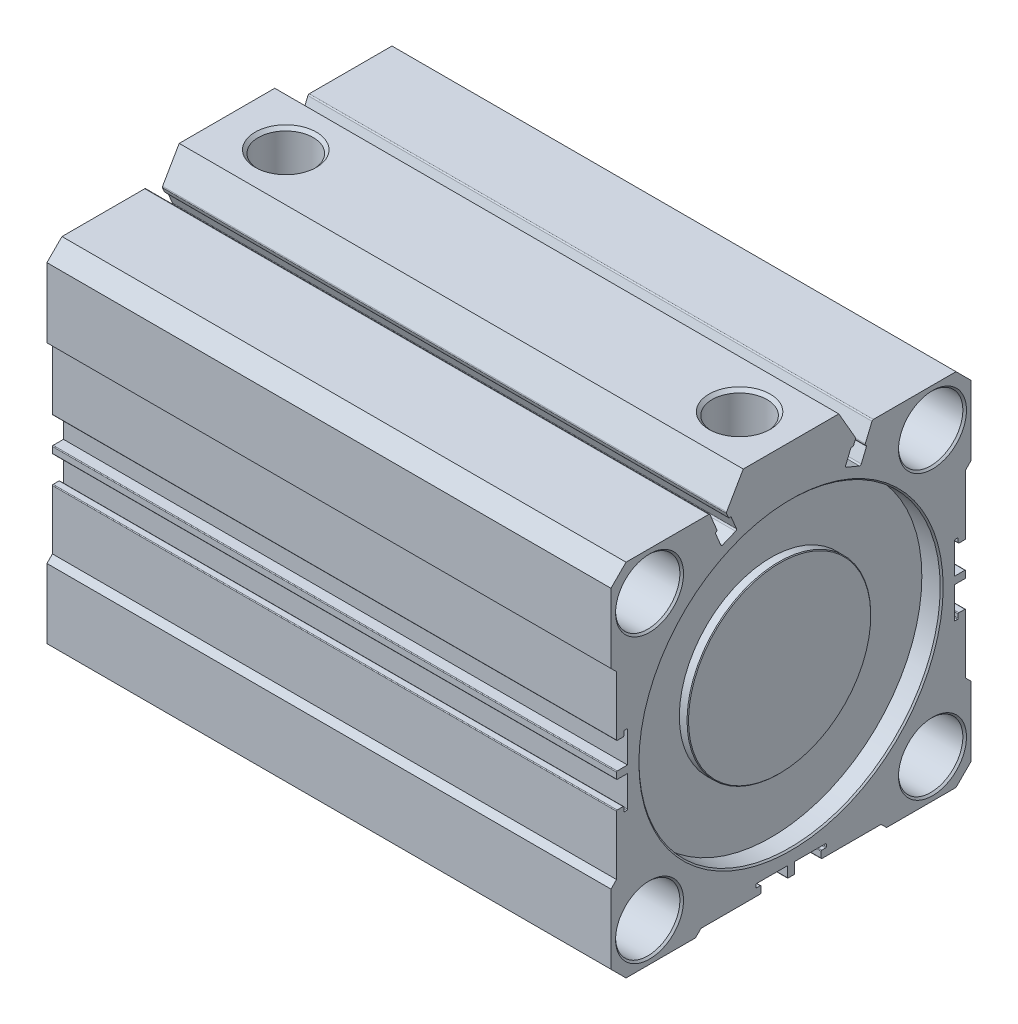
SolidWorks part; units mm, degrees
ref_plane "前视基准面" through (0, 0, 0) normal (0, 0, 1) x (1, 0, 0)
ref_plane "上视基准面" through (0, 0, 0) normal (0, 1, 0) x (1, 0, 0)
ref_plane "右视基准面" through (0, 0, 0) normal (1, 0, 0) x (0, 0, -1)
sketch "草图1" plane through (0, 0, 0) normal (1, 0, 0) x (0, 0, -1)
  line L0 (-49, -44.9) -> (-44.9, -49)
  line L1 (-44.9, -49) -> (-26, -49)
  line L2 (-26, -49) -> (-24.5, -47.5)
  line L3 (-24.5, -47.5) -> (-8.4, -47.5)
  line L4 (-8.2, -47.3) -> (-8.2, -45.7)
  line L5 (-8.4, -45.5) -> (-9.4, -45.5)
  line L6 (-9.6, -45.3) -> (-9.6, -44.7)
  line L7 (-9.4, -44.5) -> (-1, -44.5)
  line L8 (-1, -44.5) -> (-1, -47.3)
  line L9 (-0.8, -47.5) -> (0.8, -47.5)
  line L10 (1, -47.3) -> (1, -44.5)
  line L11 (1, -44.5) -> (9.4, -44.5)
  line L12 (9.6, -44.7) -> (9.6, -45.3)
  line L13 (9.4, -45.5) -> (8.4, -45.5)
  line L14 (8.2, -45.7) -> (8.2, -47.3)
  line L15 (8.4, -47.5) -> (24.5, -47.5)
  line L16 (24.5, -47.5) -> (26, -49)
  line L17 (26, -49) -> (44.9, -49)
  line L18 (44.9, -49) -> (49, -44.9)
  line L19 (49, -44.9) -> (49, -26)
  line L20 (49, -26) -> (47.5, -24.5)
  line L21 (47.5, -24.5) -> (47.5, -8.4)
  line L22 (47.3, -8.2) -> (45.7, -8.2)
  line L23 (45.5, -8.4) -> (45.5, -9.4)
  line L24 (45.3, -9.6) -> (44.7, -9.6)
  line L25 (44.5, -9.4) -> (44.5, -1)
  line L26 (44.5, -1) -> (47.3, -1)
  line L27 (47.5, -0.8) -> (47.5, 0.8)
  line L28 (47.3, 1) -> (44.5, 1)
  line L29 (44.5, 1) -> (44.5, 9.4)
  line L30 (44.7, 9.6) -> (45.3, 9.6)
  line L31 (45.5, 9.4) -> (45.5, 8.4)
  line L32 (45.7, 8.2) -> (47.3, 8.2)
  line L33 (47.5, 8.4) -> (47.5, 24.5)
  line L34 (47.5, 24.5) -> (49, 26)
  line L35 (49, 26) -> (49, 44.9)
  line L36 (49, 44.9) -> (44.9, 49)
  line L37 (44.9, 49) -> (22.4038, 49)
  line L38 (22.0343, 48.7531) -> (20.2073, 44.3424)
  line L39 (20.532, 43.5584) -> (19.1161, 40.1401)
  line L40 (18.5934, 39.9236) -> (15.0827, 41.3778)
  line L41 (14.8662, 41.9004) -> (16.2822, 45.3188)
  line L42 (17.0661, 45.6435) -> (17.5487, 46.8085)
  line L43 (17.5255, 47.1616) -> (13, 55)
  line L44 (13, 55) -> (-13, 55)
  line L45 (-13, 55) -> (-17.5255, 47.1616)
  line L46 (-17.5487, 46.8085) -> (-17.0661, 45.6435)
  line L47 (-16.2822, 45.3188) -> (-14.8662, 41.9004)
  line L48 (-15.0827, 41.3778) -> (-18.5934, 39.9236)
  line L49 (-19.1161, 40.1401) -> (-20.532, 43.5584)
  line L50 (-20.2073, 44.3424) -> (-22.0343, 48.7531)
  line L51 (-22.4038, 49) -> (-44.9, 49)
  line L52 (-44.9, 49) -> (-49, 44.9)
  line L53 (-49, 44.9) -> (-49, 26)
  line L54 (-49, 26) -> (-47.5, 24.5)
  line L55 (-47.5, 24.5) -> (-47.5, 8.4)
  line L56 (-47.3, 8.2) -> (-45.7, 8.2)
  line L57 (-45.5, 8.4) -> (-45.5, 9.4)
  line L58 (-45.3, 9.6) -> (-44.7, 9.6)
  line L59 (-44.5, 9.4) -> (-44.5, 1)
  line L60 (-44.5, 1) -> (-47.3, 1)
  line L61 (-47.5, 0.8) -> (-47.5, -0.8)
  line L62 (-47.3, -1) -> (-44.5, -1)
  line L63 (-44.5, -1) -> (-44.5, -9.4)
  line L64 (-44.7, -9.6) -> (-45.3, -9.6)
  line L65 (-45.5, -9.4) -> (-45.5, -8.4)
  line L66 (-45.7, -8.2) -> (-47.3, -8.2)
  line L67 (-47.5, -8.4) -> (-47.5, -24.5)
  line L68 (-47.5, -24.5) -> (-49, -26)
  line L69 (-49, -26) -> (-49, -44.9)
  arc A0 (-8.4, -47.5) -> (-8.2, -47.3) centre (-8.4, -47.3) ccw
  arc A1 (-8.2, -45.7) -> (-8.4, -45.5) centre (-8.4, -45.7) ccw
  arc A2 (-9.4, -45.5) -> (-9.6, -45.3) centre (-9.4, -45.3) cw
  arc A3 (-9.6, -44.7) -> (-9.4, -44.5) centre (-9.4, -44.7) cw
  arc A4 (-1, -47.3) -> (-0.8, -47.5) centre (-0.8, -47.3) ccw
  arc A5 (0.8, -47.5) -> (1, -47.3) centre (0.8, -47.3) ccw
  arc A6 (9.4, -44.5) -> (9.6, -44.7) centre (9.4, -44.7) cw
  arc A7 (9.6, -45.3) -> (9.4, -45.5) centre (9.4, -45.3) cw
  arc A8 (8.4, -45.5) -> (8.2, -45.7) centre (8.4, -45.7) ccw
  arc A9 (8.2, -47.3) -> (8.4, -47.5) centre (8.4, -47.3) ccw
  arc A10 (47.5, -8.4) -> (47.3, -8.2) centre (47.3, -8.4) ccw
  arc A11 (45.7, -8.2) -> (45.5, -8.4) centre (45.7, -8.4) ccw
  arc A12 (45.5, -9.4) -> (45.3, -9.6) centre (45.3, -9.4) cw
  arc A13 (44.7, -9.6) -> (44.5, -9.4) centre (44.7, -9.4) cw
  arc A14 (47.3, -1) -> (47.5, -0.8) centre (47.3, -0.8) ccw
  arc A15 (47.5, 0.8) -> (47.3, 1) centre (47.3, 0.8) ccw
  arc A16 (44.5, 9.4) -> (44.7, 9.6) centre (44.7, 9.4) cw
  arc A17 (45.3, 9.6) -> (45.5, 9.4) centre (45.3, 9.4) cw
  arc A18 (45.5, 8.4) -> (45.7, 8.2) centre (45.7, 8.4) ccw
  arc A19 (47.3, 8.2) -> (47.5, 8.4) centre (47.3, 8.4) ccw
  arc A20 (22.4038, 49) -> (22.0343, 48.7531) centre (22.4038, 48.6) ccw
  arc A21 (20.2073, 44.3424) -> (20.4238, 43.8197) centre (20.5768, 44.1893) ccw
  arc A22 (20.4238, 43.8197) -> (20.532, 43.5584) centre (20.3472, 43.635) cw
  arc A23 (19.1161, 40.1401) -> (18.5934, 39.9236) centre (18.7465, 40.2932) cw
  arc A24 (15.0827, 41.3778) -> (14.8662, 41.9004) centre (15.2358, 41.7473) cw
  arc A25 (16.2822, 45.3188) -> (16.5435, 45.427) centre (16.4669, 45.2422) cw
  arc A26 (16.5435, 45.427) -> (17.0661, 45.6435) centre (16.6965, 45.7966) ccw
  arc A27 (17.5487, 46.8085) -> (17.5255, 47.1616) centre (17.1791, 46.9616) ccw
  arc A28 (-17.5255, 47.1616) -> (-17.5487, 46.8085) centre (-17.1791, 46.9616) ccw
  arc A29 (-17.0661, 45.6435) -> (-16.5435, 45.427) centre (-16.6965, 45.7966) ccw
  arc A30 (-16.5435, 45.427) -> (-16.2822, 45.3188) centre (-16.4669, 45.2422) cw
  arc A31 (-14.8662, 41.9004) -> (-15.0827, 41.3778) centre (-15.2358, 41.7473) cw
  arc A32 (-18.5934, 39.9236) -> (-19.1161, 40.1401) centre (-18.7465, 40.2932) cw
  arc A33 (-20.532, 43.5584) -> (-20.4238, 43.8197) centre (-20.3472, 43.635) cw
  arc A34 (-20.4238, 43.8197) -> (-20.2073, 44.3424) centre (-20.5768, 44.1893) ccw
  arc A35 (-22.0343, 48.7531) -> (-22.4038, 49) centre (-22.4038, 48.6) ccw
  arc A36 (-47.5, 8.4) -> (-47.3, 8.2) centre (-47.3, 8.4) ccw
  arc A37 (-45.7, 8.2) -> (-45.5, 8.4) centre (-45.7, 8.4) ccw
  arc A38 (-45.5, 9.4) -> (-45.3, 9.6) centre (-45.3, 9.4) cw
  arc A39 (-44.7, 9.6) -> (-44.5, 9.4) centre (-44.7, 9.4) cw
  arc A40 (-47.3, 1) -> (-47.5, 0.8) centre (-47.3, 0.8) ccw
  arc A41 (-47.5, -0.8) -> (-47.3, -1) centre (-47.3, -0.8) ccw
  arc A42 (-44.5, -9.4) -> (-44.7, -9.6) centre (-44.7, -9.4) cw
  arc A43 (-45.3, -9.6) -> (-45.5, -9.4) centre (-45.3, -9.4) cw
  arc A44 (-45.5, -8.4) -> (-45.7, -8.2) centre (-45.7, -8.4) ccw
  arc A45 (-47.3, -8.2) -> (-47.5, -8.4) centre (-47.3, -8.4) ccw
extrude "凸台-拉伸1" add sketch "草图1" along normal blind 153.5
ref_plane "基准面1" through (0, 0, 38.5) normal (0, 0, 1) x (1, 0, 0)
sketch "草图2" plane through (0, 0, 38.5) normal (0, 0, 1) x (1, 0, 0)
  line L0 (0, -38.5) -> (0, -29.25)
  line L1 (0, -29.25) -> (0.5, -29.75)
  line L2 (0.5, -29.75) -> (13.5, -29.75)
  line L3 (13.5, -29.75) -> (13.5, -32.5)
  line L4 (13.5, -32.5) -> (14.447, -33.447)
  line L5 (14.447, -33.447) -> (76.75, -33.447)
  line L6 (76.75, -33.447) -> (76.75, -38.5)
  line L7 (76.75, -38.5) -> (0, -38.5)
  line L8 (76.75, -38.5) -> (0, -38.5) construction
revolve "切除-旋转1" cut sketch "草图2" angle 360 about L8 reverse direction yes
cosmetic thread "装饰螺纹线1" parameters "D1"=22, "D2"=12
cosmetic thread "装饰螺纹线2" parameters "D1"=22, "D2"=12
sketch "草图3" plane through (0, 0, 0) normal (1, 0, 0) x (0, 0, -1)
  line L0 (-38.5, -38.5) -> (38.5, -38.5)
  line L1 (-38.5, -38.5) -> (-38.5, 38.5)
pattern_linear "阵列(线性)1" count 2 spacing 77 along (0, 0, -1) count 2 spacing 77 along (0, 1, 0) of "切除-旋转1"
sketch "草图4" plane through (0, 0, 38.5) normal (0, 0, 1) x (1, 0, 0)
  line L0 (76.75, -38.5) -> (76.75, -33.447)
  line L1 (76.75, -33.447) -> (139.053, -33.447)
  line L2 (139.053, -33.447) -> (140, -32.5)
  line L3 (140, -32.5) -> (140, -29.75)
  line L4 (140, -29.75) -> (153, -29.75)
  line L5 (153, -29.75) -> (153.5, -29.25)
  line L6 (153.5, -29.25) -> (153.5, -38.5)
  line L7 (153.5, -38.5) -> (76.75, -38.5)
  line L8 (153.5, -38.5) -> (76.75, -38.5) construction
revolve "切除-旋转2" cut sketch "草图4" angle 360 about L8 reverse direction yes
ref_plane "基准面2" through (153.5, 0, 0) normal (1, 0, 0) x (0, 0, -1)
sketch "草图5" plane through (153.5, 0, 0) normal (1, 0, 0) x (0, 0, -1)
  line L0 (-38.5, -38.5) -> (38.5, -38.5)
  line L1 (-38.5, -38.5) -> (-38.5, 38.5)
pattern_linear "阵列(线性)2" count 2 spacing 77 along (0, 0, -1) count 2 spacing 77 along (0, 1, 0) of "切除-旋转2"
sketch "草图6" plane through (0, 0, 0) normal (0, 0, 1) x (1, 0, 0)
  line L0 (0, 0) -> (0, 12.5)
  line L1 (0, 12.5) -> (15.4, 12.5)
  line L2 (15.4, 12.5) -> (15.4, 40)
  line L3 (15.4, 40) -> (142.5, 40)
  line L4 (142.5, 40) -> (142.5, 0)
  line L5 (142.5, 0) -> (0, 0)
  line L6 (142.5, 0) -> (0, 0) construction
revolve "切除-旋转3" cut sketch "草图6" angle 360 about L6 reverse direction yes
sketch "草图7" plane through (0, 0, 0) normal (0, 0, 1) x (1, 0, 0)
  line L0 (0, 0) -> (0, 41.4)
  line L1 (0, 41.4) -> (0.4, 41)
  line L2 (0.4, 41) -> (5.4, 41)
  line L3 (5.4, 41) -> (5.4, 0)
  line L4 (5.4, 0) -> (0, 0)
  line L5 (5.4, 0) -> (0, 0) construction
revolve "切除-旋转4" cut sketch "草图7" angle 360 about L5 reverse direction yes
ref_plane "基准面3" through (2.9, 0, 0) normal (1, 0, 0) x (0, 0, -1)
hole_wizard "孔1" positions "草图9" profile "草图8" legacy
sketch "草图9" plane through (0, 55, 0) normal (0, 1, 0) x (1, 0, 0)
  point P0 (16, 0)
sketch "草图8" plane through (16, 55, 0) normal (1, 0, 0) x (0, 0, 1)
  line L0 (0, 0) -> (0, 12)
  line L1 (0, 12) -> (7.475, 12)
  line L2 (7.475, 12) -> (7.475, 0.856)
  line L3 (7.475, 0.856) -> (8.331, 0)
  line L4 (8.331, 0) -> (0, 0)
  line L5 (0, -6.4453) -> (0, 115.525) construction
  line L6 (-7.475, 0.856) -> (-8.331, 0) construction
  dimension "直径" = 14.95
  dimension "深度" = 12
  dimension "锥坑角度" = 90
  dimension "锥坑直径" = 16.662
cosmetic thread "装饰螺纹线3" parameters "D1"=12, "D2"=16.662
hole_wizard "孔2" positions "草图11" profile "草图10" legacy
sketch "草图11" plane through (0, 55, 0) normal (0, 1, 0) x (1, 0, 0)
  point P0 (139.5, 0)
sketch "草图10" plane through (139.5, 55, 0) normal (1, 0, 0) x (0, 0, 1)
  line L0 (0, 0) -> (0, 12)
  line L1 (0, 12) -> (7.475, 12)
  line L2 (7.475, 12) -> (7.475, 0.856)
  line L3 (7.475, 0.856) -> (8.331, 0)
  line L4 (8.331, 0) -> (0, 0)
  line L5 (0, -6.4453) -> (0, 115.525) construction
  line L6 (-7.475, 0.856) -> (-8.331, 0) construction
  dimension "直径" = 14.95
  dimension "深度" = 12
  dimension "锥坑角度" = 90
  dimension "锥坑直径" = 16.662
cosmetic thread "装饰螺纹线4" parameters "D1"=12, "D2"=16.662
sketch "草图12" plane through (0, 0, 0) normal (0, 0, 1) x (1, 0, 0)
  line L0 (0.7, 12.5) -> (5.4, 12.5)
  line L1 (5.4, 12.5) -> (5.4, 25)
  line L2 (5.4, 25) -> (1.7, 25)
  line L3 (0.7, 24) -> (0.7, 12.5)
  line L4 (5.4, 0) -> (0.7, 0) construction
  arc A0 (1.7, 25) -> (0.7, 24) centre (1.7, 24) ccw
revolve "旋转1" add sketch "草图12" angle 360 about L4 reverse direction yes
hole_wizard "孔3" positions "草图14" profile "草图13" legacy
sketch "草图14" plane through (153.5, 0, 0) normal (1, 0, 0) x (0, 0, -1)
  point P0 (0, 0)
sketch "草图13" plane through (153.5, 0, 0) normal (0, 1, 0) x (0, 0, -1)
  line L0 (0, 0) -> (0, 5.4)
  line L1 (0, 5.4) -> (41, 5.4)
  line L2 (41, 5.4) -> (41, 0.4)
  line L3 (41, 0.4) -> (41.4, 0)
  line L4 (41.4, 0) -> (0, 0)
  line L5 (0, -6.4453) -> (0, 115.525) construction
  line L6 (-41, 0.4) -> (-41.4, 0) construction
  dimension "直径" = 82
  dimension "深度" = 5.4
  dimension "锥坑角度" = 90
  dimension "锥坑直径" = 82.8
ref_plane "基准面4" through (153.5, 0, 0) normal (1, 0, 0) x (0, 0, -1)
ref_plane "基准面5" through (0, 34, 0) normal (0, 1, 0) x (1, 0, 0)
ref_plane "基准面6" through (150.6, 0, 0) normal (1, 0, 0) x (0, 0, -1)
sketch "草图15" plane through (0, 0, 0) normal (0, 0, 1) x (1, 0, 0)
  line L0 (148.1, 0) -> (148.1, 25)
  line L1 (148.1, 25) -> (150.2, 25)
  line L2 (150.2, 25) -> (150.4, 24.8)
  line L3 (150.4, 24.8) -> (150.4, 0)
  line L4 (150.4, 0) -> (148.1, 0)
  line L5 (150.4, 0) -> (148.1, 0) construction
revolve "旋转2" add sketch "草图15" angle 360 about L5 reverse direction yes
ref_plane "基准面7" through (1, 0, 0) normal (1, 0, 0) x (0, 0, -1)
ref_plane "基准面8" through (152.5, 0, 0) normal (1, 0, 0) x (0, 0, -1)
ref_plane "IP_SWITCH1 XY" through (1, 0, 0) normal (-1, 0, 0) x (0, 0, 1)
ref_plane "IP_SWITCH1 XZ" through (0, 40.6507, 0) normal (0, 1, 0) x (1, 0, 0)
ref_plane "IP_SWITCH1 YZ" through (0, 0, -16.8381) normal (0, 0, -1) x (-1, 0, 0)
ref_axis "IP_SWITCH1 X" through (1, 40.6507, 80.9) along (0, 0, -1)
ref_axis "IP_SWITCH1 Y" through (1, 50, -16.8381) along (0, -1, 0)
ref_axis "IP_SWITCH1 Z" through (-80.9, 40.6507, -16.8381) along (1, 0, 0)
sketch3d "IP_SWITCH1"
  point P0 (1, 40.6507, -16.8381)
ref_plane "IP_SWITCH2 XY" through (152.5, 0, 0) normal (1, 0, 0) x (0, 0, -1)
ref_plane "IP_SWITCH2 XZ" through (0, 40.6507, 0) normal (0, -1, 0) x (-1, 0, 0)
ref_plane "IP_SWITCH2 YZ" through (0, 0, 16.8381) normal (0, 0, -1) x (-1, 0, 0)
ref_axis "IP_SWITCH2 X" through (152.5, 40.6507, 80.9) along (0, 0, -1)
ref_axis "IP_SWITCH2 Y" through (152.5, -50, 16.8381) along (0, 1, 0)
ref_axis "IP_SWITCH2 Z" through (80.9, 40.6507, 16.8381) along (-1, 0, 0)
sketch3d "IP_SWITCH2"
  point P0 (152.5, 40.6507, 16.8381)
ref_plane "IP_SWITCH3 XY" through (1, 0, 0) normal (-1, 0, 0) x (0, 0, 1)
ref_plane "IP_SWITCH3 XZ" through (0, 1, 0) normal (0, 1, 0) x (1, 0, 0)
ref_plane "IP_SWITCH3 YZ" through (0, 0, -44.5) normal (0, 0, -1) x (-1, 0, 0)
ref_axis "IP_SWITCH3 X" through (1, 1, 80.9) along (0, 0, -1)
ref_axis "IP_SWITCH3 Y" through (1, 50, -44.5) along (0, -1, 0)
ref_axis "IP_SWITCH3 Z" through (-80.9, 1, -44.5) along (1, 0, 0)
sketch3d "IP_SWITCH3"
  point P0 (1, 1, -44.5)
ref_plane "IP_SWITCH4 XY" through (152.5, 0, 0) normal (1, 0, 0) x (0, 0, -1)
ref_plane "IP_SWITCH4 XZ" through (0, -1, 0) normal (0, -1, 0) x (-1, 0, 0)
ref_plane "IP_SWITCH4 YZ" through (0, 0, 44.5) normal (0, 0, -1) x (-1, 0, 0)
ref_axis "IP_SWITCH4 X" through (152.5, -1, 80.9) along (0, 0, -1)
ref_axis "IP_SWITCH4 Y" through (152.5, -50, 44.5) along (0, 1, 0)
ref_axis "IP_SWITCH4 Z" through (80.9, -1, 44.5) along (-1, 0, 0)
sketch3d "IP_SWITCH4"
  point P0 (152.5, -1, 44.5)
ref_plane "for_dummy XY" through (0, 0, 0) normal (-1, 0, 0) x (0, 0, 1)
ref_plane "for_dummy XZ" through (0, 0, 0) normal (0, 1, 0) x (1, 0, 0)
ref_plane "for_dummy YZ" through (0, 0, 0) normal (0, 0, -1) x (-1, 0, 0)
ref_axis "for_dummy X" through (0, 0, 80.9) along (0, 0, -1)
ref_axis "for_dummy Y" through (0, 50, 0) along (0, -1, 0)
ref_axis "for_dummy Z" through (-80.9, 0, 0) along (1, 0, 0)
sketch3d "for_dummy"
  point P0 (0, 0, 0)
ref_plane "for_mouanting XY" through (153.5, 0, 0) normal (1, 0, 0) x (0, 0, -1)
ref_plane "for_mouanting XZ" through (0, 0, 0) normal (0, -1, 0) x (-1, 0, 0)
ref_plane "for_mouanting YZ" through (0, 0, 0) normal (0, 0, -1) x (-1, 0, 0)
ref_axis "for_mouanting X" through (153.5, 0, 80.9) along (0, 0, -1)
ref_axis "for_mouanting Y" through (153.5, -50, 0) along (0, 1, 0)
ref_axis "for_mouanting Z" through (80.9, 0, 0) along (-1, 0, 0)
sketch3d "for_mouanting"
  point P0 (153.5, 0, 0)
ref_plane "for_s XY" through (0, 34, 0) normal (0, 1, 0) x (1, 0, 0)
ref_plane "for_s XZ" through (0, 0, 0) normal (0, 0, 1) x (1, 0, 0)
ref_plane "for_s YZ" through (16, 0, 0) normal (1, 0, 0) x (0, 0, -1)
ref_axis "for_s X" through (-80.9, 34, 0) along (1, 0, 0)
ref_axis "for_s Y" through (16, 34, 50) along (0, 0, -1)
ref_axis "for_s Z" through (16, 50, 0) along (0, -1, 0)
sketch3d "for_s"
  point P0 (16, 34, 0)
ref_plane "for_s_2 XY" through (0, 34, 0) normal (0, 1, 0) x (1, 0, 0)
ref_plane "for_s_2 XZ" through (0, 0, 0) normal (0, 0, 1) x (1, 0, 0)
ref_plane "for_s_2 YZ" through (139.5, 0, 0) normal (1, 0, 0) x (0, 0, -1)
ref_axis "for_s_2 X" through (-80.9, 34, 0) along (1, 0, 0)
ref_axis "for_s_2 Y" through (139.5, 34, 50) along (0, 0, -1)
ref_axis "for_s_2 Z" through (139.5, 50, 0) along (0, -1, 0)
sketch3d "for_s_2"
  point P0 (139.5, 34, 0)
